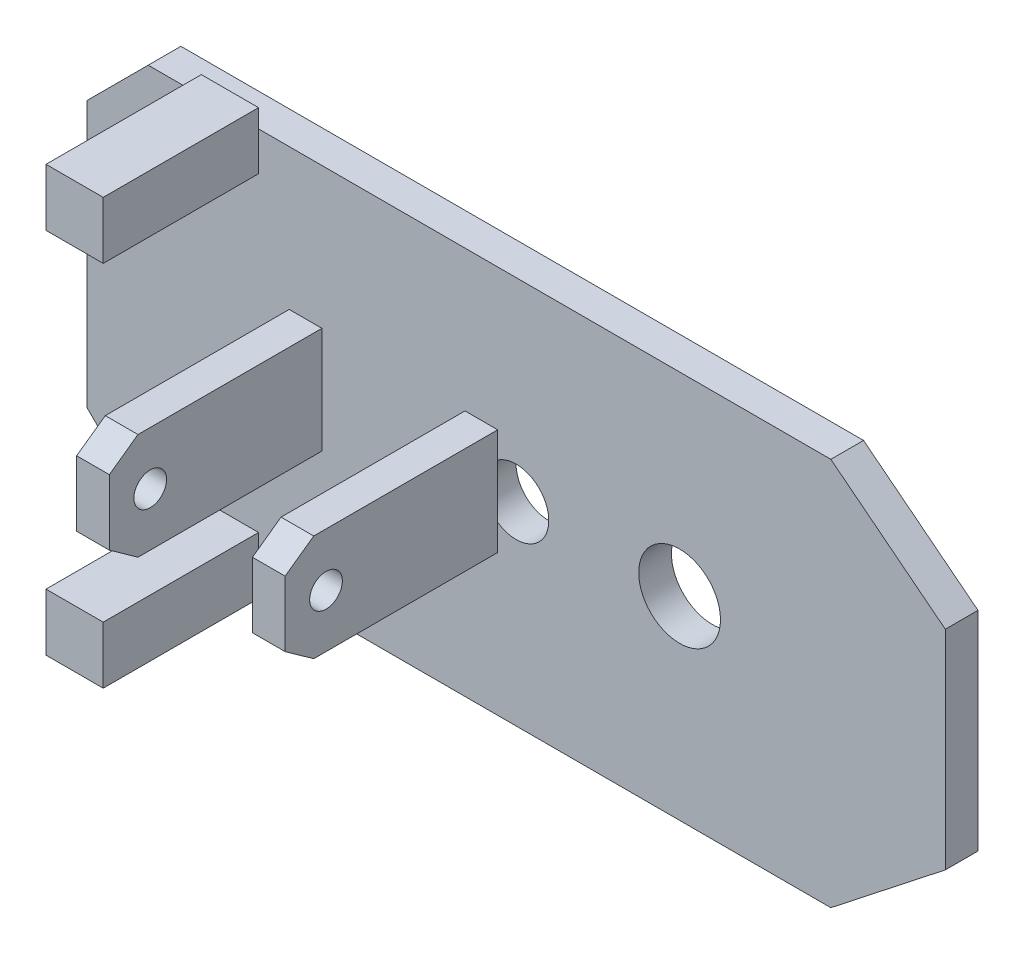
SolidWorks part; units mm, degrees
ref_plane "Front Plane" through (0, 0, 0) normal (0, 0, 1) x (1, 0, 0)
ref_plane "Top Plane" through (0, 0, 0) normal (0, 1, 0) x (1, 0, 0)
ref_plane "Right Plane" through (0, 0, 0) normal (1, 0, 0) x (0, 0, -1)
ref_plane "PL_Sole_Plate_base" through (0, 0, -50) normal (0, 0, 1) x (1, 0, 0)
sketch "SK_Sole_Plate" plane through (0, 0, -50) normal (0, 0, 1) x (1, 0, 0)
  line L0 (-60, -47.5) -> (107, -47.5)
  line L1 (107, -47.5) -> (135, -25.5)
  line L2 (135, -25.5) -> (135, 25.5)
  line L3 (135, 25.5) -> (107, 47.5)
  line L4 (107, 47.5) -> (-60, 47.5)
  line L5 (-60, 47.5) -> (-75, 32.5)
  line L6 (-75, 32.5) -> (-75, -32.5)
  line L7 (-75, -32.5) -> (-60, -47.5)
  circle A0 centre (70, 0) radius 10
  circle A1 centre (30, 0) radius 8
  dimension "D17_SK_Sole_Plate" = 20
  dimension "D19_SK_Sole_Plate" = 16
  dimension "P1" = 60
  dimension "P2" = 47.5
  dimension "P3" = 107
  dimension "P4" = 47.5
  dimension "P5" = 135
  dimension "P6" = 25.5
  dimension "P7" = 135
  dimension "P8" = 25.5
  dimension "P9" = 107
  dimension "P10" = 47.5
  dimension "P11" = 60
  dimension "P12" = 47.5
  dimension "P13" = 75
  dimension "P14" = 32.5
  dimension "P15" = 75
  dimension "P16" = 32.5
  dimension "P18" = 70
  dimension "P20" = 30
extrude "Sole_Plate" add sketch "SK_Sole_Plate" along normal blind 8
ref_plane "PL_Clevis_Front_base" through (17.5, 0, 0) normal (1, 0, 0) x (0, 0, -1)
sketch "SK_Clevis_Front" plane through (17.5, 0, 0) normal (1, 0, 0) x (0, 0, -1)
  line L0 (42, -13) -> (42, 13)
  line L1 (42, 13) -> (-3, 13)
  line L2 (-3, 13) -> (-10, 8)
  line L3 (-10, 8) -> (-10, -8)
  line L4 (-10, -8) -> (-3, -13)
  line L5 (-3, -13) -> (42, -13)
  circle A0 centre (0, 0) radius 4
  dimension "D13_SK_Clevis_Front" = 8
  dimension "P1" = 42
  dimension "P2" = 13
  dimension "P3" = 42
  dimension "P4" = 13
  dimension "P5" = 3
  dimension "P6" = 13
  dimension "P7" = 10
  dimension "P8" = 8
  dimension "P9" = 10
  dimension "P10" = 8
  dimension "P11" = 3
  dimension "P12" = 13
extrude "Clevis_Front" add sketch "SK_Clevis_Front" along normal blind 8
ref_plane "PL_Clevis_Back_base" through (-25.5, 0, 0) normal (1, 0, 0) x (0, 0, -1)
sketch "SK_Clevis_Back" plane through (-25.5, 0, 0) normal (1, 0, 0) x (0, 0, -1)
  line L0 (42, -13) -> (42, 13)
  line L1 (42, 13) -> (-3, 13)
  line L2 (-3, 13) -> (-10, 8)
  line L3 (-10, 8) -> (-10, -8)
  line L4 (-10, -8) -> (-3, -13)
  line L5 (-3, -13) -> (42, -13)
  circle A0 centre (0, 0) radius 4
  dimension "D13_SK_Clevis_Back" = 8
  dimension "P1" = 42
  dimension "P2" = 13
  dimension "P3" = 42
  dimension "P4" = 13
  dimension "P5" = 3
  dimension "P6" = 13
  dimension "P7" = 10
  dimension "P8" = 8
  dimension "P9" = 10
  dimension "P10" = 8
  dimension "P11" = 3
  dimension "P12" = 13
extrude "Clevis_Back" add sketch "SK_Clevis_Back" along normal blind 8
ref_plane "PL_Post_Lat_base" through (0, 0, -42) normal (0, 0, 1) x (1, 0, 0)
sketch "SK_Post_Lat" plane through (0, 0, -42) normal (0, 0, 1) x (1, 0, 0)
  line L0 (-47, 38) -> (-33, 38)
  line L1 (-33, 38) -> (-33, 52)
  line L2 (-33, 52) -> (-47, 52)
  line L3 (-47, 52) -> (-47, 38)
  dimension "P1" = 47
  dimension "P2" = 38
  dimension "P3" = 33
  dimension "P4" = 38
  dimension "P5" = 33
  dimension "P6" = 52
  dimension "P7" = 47
  dimension "P8" = 52
extrude "Post_Lat" add sketch "SK_Post_Lat" along normal blind 38
ref_plane "PL_Post_Med_base" through (0, 0, -42) normal (0, 0, 1) x (1, 0, 0)
sketch "SK_Post_Med" plane through (0, 0, -42) normal (0, 0, 1) x (1, 0, 0)
  line L0 (-47, -52) -> (-33, -52)
  line L1 (-33, -52) -> (-33, -38)
  line L2 (-33, -38) -> (-47, -38)
  line L3 (-47, -38) -> (-47, -52)
  dimension "P1" = 47
  dimension "P2" = 52
  dimension "P3" = 33
  dimension "P4" = 52
  dimension "P5" = 33
  dimension "P6" = 38
  dimension "P7" = 47
  dimension "P8" = 38
extrude "Post_Med" add sketch "SK_Post_Med" along normal blind 38
ref_axis "AX_Roll" through (-85.5, 0, 0) along (1, 0, 0)
sketch "SK_RodBalls" plane through (0, 0, 0) normal (0, 0, 1) x (1, 0, 0)
  point P0 (-40, 45)
  point P2 (-40, -45)
  dimension "P1" = 40
  dimension "P2" = 45
  dimension "P3" = 40
  dimension "P4" = 45
equation "\"Foot_length\" = 210"
equation "\"Foot_width\" = 95"
equation "\"Ankle_height\" = 50"
